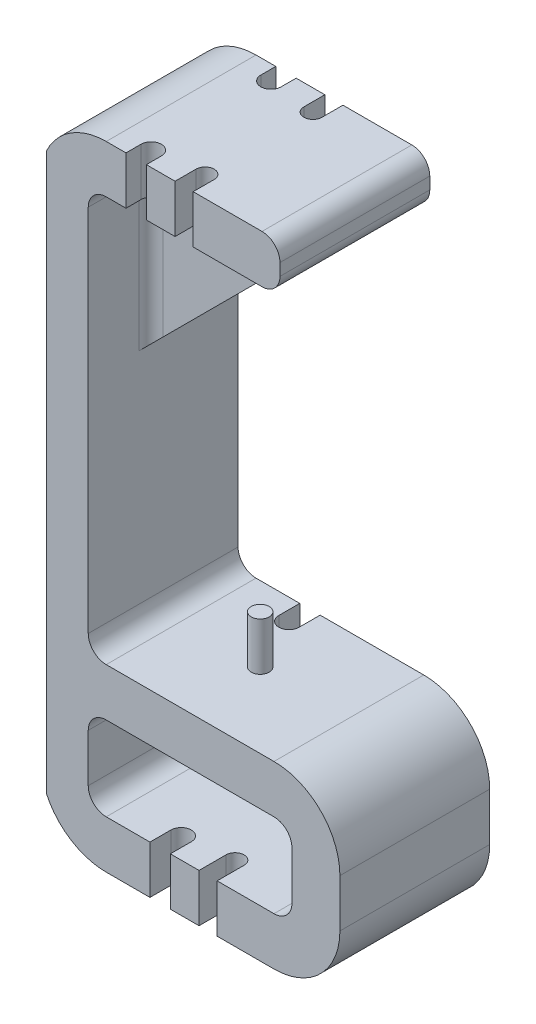
SolidWorks part; units mm, degrees
material "PPS"
ref_plane "Front" through (0, 0, 0) normal (0, 0, 1) x (1, 0, 0)
ref_plane "Top" through (0, 0, 0) normal (0, 1, 0) x (1, 0, 0)
ref_plane "Right" through (0, 0, 0) normal (1, 0, 0) x (0, 0, -1)
sketch "Sketch6" plane through (0, 0, 0) normal (0, 0, 1) x (1, 0, 0)
  line L0 (-25, 52.805) -> (15, 52.805)
  line L1 (15, 52.805) -> (15, 44.805)
  line L2 (15, 44.805) -> (-17, 44.805)
  line L3 (-17, 44.805) -> (-17, -44.805)
  line L4 (-17, -44.805) -> (25, -44.805)
  line L5 (25, -44.805) -> (25, -52.805)
  line L6 (25, -52.805) -> (-25, -52.805)
  line L7 (-25, -52.805) -> (-25, 52.805)
  line L8 (-25, 52.805) -> (25, -52.805) construction
  dimension "D1" = 105.61
  dimension "D2" = 8
  dimension "D3" = 8
  dimension "D4" = 50
  dimension "D5" = 40
extrude "Boss-Extrude2" add sketch "Sketch6" along normal mid plane 25
sketch "Sketch15" plane through (0, 0, 12.5) normal (0, 0, 1) x (1, 0, 0)
  line L1 (-17, -22.805) -> (25, -22.805)
  line L3 (-17, -44.805) -> (-17, 44.805) construction
  line L4 (25, -22.805) -> (25, -52.805)
  line L5 (25, -52.805) -> (17, -52.805)
  line L6 (-17, -22.805) -> (-17, -30.805)
  line L7 (-17, -44.805) -> (-17, 44.805) construction
  line L8 (-17, -30.805) -> (17, -30.805)
  line L9 (17, -30.805) -> (17, -52.805)
  point P34 (25, -22.805)
  dimension "D1" = 30
  dimension "D2" = 8
  dimension "D3" = 8
extrude "Boss-Extrude3" add sketch "Sketch15" against normal up to surface (25 mm away) up to face at (-0.5, 0, -12.5)
fillet "Fillet3" radius 3 6 edges at (-17, 44.805, 0) (-17, -44.805, 0) (17, -44.805, 0) (17, -30.805, 0) (-17, -30.805, 0) (-17, -22.805, 0)
fillet "Fillet4" radius 11 4 edges at (-25, -52.805, 0) (25, -22.805, 0) (25, -52.805, 0) (-25, 52.805, 0)
sketch "Sketch20" plane through (0, 52.805, 0) normal (0, 1, 0) x (1, 0, 0)
  line L0 (-10.7, 12.5) -> (-10.7, 10)
  line L1 (15, 12.5) -> (-14, 12.5) construction
  line L2 (-7.3, 10) -> (-7.3, 12.5)
  line L3 (-7.3, 12.5) -> (-10.7, 12.5)
  line L4 (0, 0) -> (15, 0) construction
  line L5 (15, -12.5) -> (15, 12.5) construction
  line L6 (-7.3, -12.5) -> (-10.7, -12.5)
  line L7 (-7.3, -10) -> (-7.3, -12.5)
  line L8 (-10.7, -12.5) -> (-10.7, -10)
  line L9 (-9, -10) -> (-9, 10) construction
  line L10 (-25, -12.5) -> (-25, 12.5) construction
  arc A0 (-10.7, 10) -> (-7.3, 10) centre (-9, 10) ccw
  arc A1 (-10.7, -10) -> (-7.3, -10) centre (-9, -10) cw
  dimension "D1" = 1.7
  dimension "D2" = 20
  dimension "D3" = 16
extrude "Cut-Extrude2" cut sketch "Sketch20" against normal up to next
sketch "Sketch21" plane through (0, -52.805, 0) normal (0, -1, 0) x (1, 0, 0)
  line L0 (-6.7, 12.5) -> (-6.7, 9) construction
  line L1 (-14, 12.5) -> (14, 12.5) construction
  line L2 (-3.3, 9) -> (-3.3, 12.5) construction
  line L3 (-3.3, 12.5) -> (-6.7, 12.5) construction
  line L4 (-5, -9) -> (-5, 9) construction
  line L5 (0, 0) -> (14, 0) construction
  line L6 (14, -12.5) -> (14, 12.5) construction
  line L7 (-3.3, -12.5) -> (-6.7, -12.5)
  line L8 (-3.3, -9) -> (-3.3, -12.5)
  line L9 (-6.7, -12.5) -> (-6.7, -9)
  line L10 (-25, -12.5) -> (-25, 12.5) construction
  arc A0 (-6.7, 9) -> (-3.3, 9) centre (-5, 9) ccw construction
  arc A1 (-6.7, -9) -> (-3.3, -9) centre (-5, -9) cw
  dimension "D1" = 1.7
  dimension "D2" = 18
  dimension "D3" = 20
extrude "Cut-Extrude3" cut sketch "Sketch21" against normal up to surface (30 mm away) up to face at (0, -22.805, 0)
sketch "Sketch25" plane through (0, -52.805, 0) normal (0, -1, 0) x (1, 0, 0)
  line L0 (-3.3, 9) -> (-3.3, 12.5) construction
  line L1 (-3.3, 12.5) -> (-6.7, 12.5) construction
  line L2 (-6.7, 12.5) -> (-6.7, 9) construction
  line L3 (-3.3, 9) -> (-3.3, 12.5)
  line L4 (-3.3, 12.5) -> (-6.7, 12.5)
  line L5 (-6.7, 12.5) -> (-6.7, 9)
  arc A0 (-6.7, 9) -> (-3.3, 9) centre (-5, 9) ccw construction
  arc A1 (-6.7, 9) -> (-3.3, 9) centre (-5, 9) ccw
extrude "Cut-Extrude7" cut sketch "Sketch25" against normal up to next
sketch "Sketch22" plane through (0, 0, 0) normal (0, 0, 1) x (1, 0, 0)
  line L0 (11, 44.805) -> (-17, 16.805)
  line L1 (-7.3, 44.805) -> (15, 44.805) construction
  line L2 (-17, -19.805) -> (-17, 41.805) construction
  line L3 (-17, 16.805) -> (-17, 41.805)
  line L4 (-14, 44.805) -> (11, 44.805)
  arc A0 (-17, 41.805) -> (-14, 44.805) centre (-14, 41.805) cw
  dimension "D1" = 28
extrude "Boss-Extrude5" add sketch "Sketch22" along normal mid plane 4
fillet "Fillet6" radius 2 6 edges at (-17, 29.305, -2) (-16.1213, 43.9263, -2) (-1.5, 44.805, 2) (-16.1213, 43.9263, 2) (-1.5, 44.805, -2) (-17, 29.305, 2)
fillet "Fillet7" radius 3 2 edges at (15, 52.805, 0) (15, 44.805, 0)
sketch "Sketch23" plane through (0, 52.805, 0) normal (0, 1, 0) x (1, 0, 0)
  line L0 (-2.51, 12.5) -> (-2.51, 9)
  line L1 (12, 12.5) -> (-7.3, 12.5) construction
  line L2 (0.51, 9) -> (0.51, 12.5)
  line L3 (0.51, 12.5) -> (-2.51, 12.5)
  line L4 (-9, 10) -> (-1, 10) construction
  line L5 (-1, 10) -> (-1, 9) construction
  line L6 (0, 0) -> (12, 0) construction
  line L7 (12, -12.5) -> (12, 12.5) construction
  line L8 (0.51, -12.5) -> (-2.51, -12.5)
  line L9 (0.51, -9) -> (0.51, -12.5)
  line L10 (-2.51, -12.5) -> (-2.51, -9)
  arc A0 (-2.51, 9) -> (0.51, 9) centre (-1, 9) ccw
  arc A1 (-2.51, -9) -> (0.51, -9) centre (-1, -9) cw
  dimension "D1" = 1.51
  dimension "D2" = 8
  dimension "D3" = 1
extrude "Cut-Extrude4" cut sketch "Sketch23" against normal up to next
sketch "Sketch24" plane through (0, -52.805, 0) normal (0, -1, 0) x (1, 0, 0)
  line L0 (1.49, -12.5) -> (1.49, -8)
  line L1 (-3.3, -12.5) -> (14, -12.5) construction
  line L2 (4.51, -8) -> (4.51, -12.5)
  line L3 (4.51, -12.5) -> (1.49, -12.5)
  line L4 (3, -8) -> (3, -9) construction
  line L5 (3, -9) -> (-5, -9) construction
  line L6 (0, 0) -> (14, 0) construction
  line L7 (14, -12.5) -> (14, 12.5) construction
  line L9 (4.51, 12.5) -> (1.49, 12.5)
  line L10 (4.51, 8) -> (4.51, 12.5)
  line L11 (1.49, 12.5) -> (1.49, 8)
  arc A0 (1.49, -8) -> (4.51, -8) centre (3, -8) cw
  arc A1 (1.49, 8) -> (4.51, 8) centre (3, 8) ccw
  dimension "D1" = 1.51
  dimension "D2" = 8
  dimension "D3" = 1
extrude "Cut-Extrude6" cut sketch "Sketch24" against normal up to next
sketch "Sketch26" plane through (0, -22.805, 0) normal (0, 1, 0) x (1, 0, 0)
  line L0 (0, 0) -> (-0.8, 0) construction
  line L1 (-25, 12.5) -> (-25, -12.5) construction
  circle A0 centre (-0.8, 0) radius 1.5
  dimension "D1" = 3
  dimension "D2" = 25.7
extrude "Boss-Extrude6" add sketch "Sketch26" along normal blind 8
sketch "Sketch28" plane through (0, 52.805, 0) normal (0, 1, 0) x (1, 0, 0)
  line L0 (-10.7, 10) -> (-7.3, 10) construction
  line L1 (-10.7, -10) -> (-7.3, -10) construction
  line L2 (-7.3, -12.5) -> (-7.3, -10) construction
  arc A0 (-10.7, 10) -> (-7.3, 10) centre (-9, 10) ccw construction
  arc A1 (-7.3, -10) -> (-10.7, -10) centre (-9, -10) ccw construction
sketch "Sketch29" plane through (-25, 0, 0) normal (-1, 0, 0) x (0, 0, 1)
  line L0 (0, 41.805) -> (0, -41.805) construction
  line L1 (12.5, 41.805) -> (-12.5, 41.805) construction
  line L2 (-12.5, -41.805) -> (12.5, -41.805) construction
  text T0 "  Hyper-K Canada - Pillar V2.1 - 30/Jul/2019" font "@Adobe Heiti Std R" height 2.5
extrude "Cut-Extrude8" cut sketch "Sketch29" against normal blind 2
sketch "Sketch30" plane through (-25, 0, 0) normal (-1, 0, 0) x (0, 0, 1)
  line L0 (-12.5, -52.805) -> (12.5, -52.805)
  line L1 (12.5, -52.805) -> (12.5, 52.805)
  line L2 (12.5, 52.805) -> (-12.5, 52.805)
  line L3 (-12.5, 52.805) -> (-12.5, -52.805)
extrude "Cut-Extrude9" cut sketch "Sketch30" against normal blind 1
